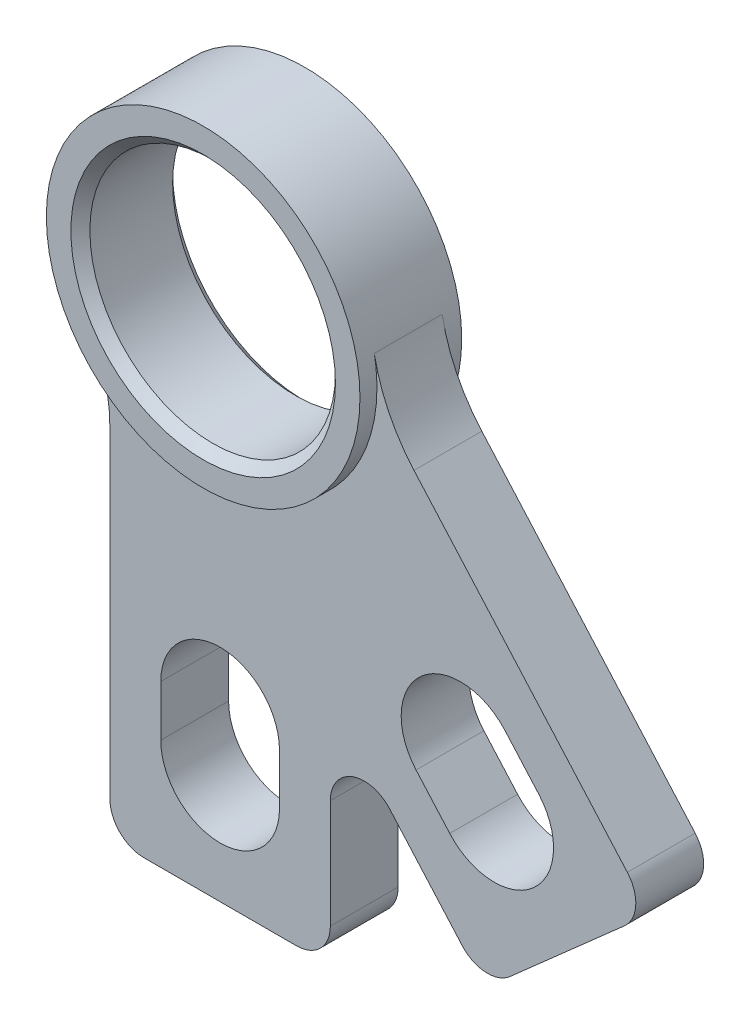
SolidWorks part; units mm, degrees
material "AISI 4130 Steel, annealed at 865C"
ref_plane "X-Y Datum" through (0, 0, 0) normal (0, 0, 1) x (1, 0, 0)
ref_plane "X-Z Datum" through (0, 0, 0) normal (0, 1, 0) x (1, 0, 0)
ref_plane "Y-Z Datum" through (0, 0, 0) normal (1, 0, 0) x (0, 0, -1)
sketch "Sketch1" plane through (0, 0, 0) normal (0, 0, 1) x (1, 0, 0)
  line L0 (0, -38.6896) -> (0, -33.9271) construction
  line L1 (-5.5562, -38.6896) -> (-5.5562, -33.9271)
  line L2 (5.5562, -38.6896) -> (5.5562, -33.9271)
  line L3 (25.6601, -29.0407) -> (22.5066, -25.4718) construction
  line L4 (21.4963, -32.7197) -> (18.3429, -29.1508)
  line L5 (29.8238, -25.3617) -> (26.6703, -21.7927)
  line L6 (-10.3187, -15.7343) -> (-10.3187, -49.0083)
  line L7 (-10.3187, -49.0083) -> (10.3187, -49.0083)
  line L10 (24.7599, -43.6058) -> (40.2252, -29.9408)
  line L11 (40.2252, -29.9408) -> (18.151, -4.9585)
  line L12 (10.3187, -49.0083) -> (10.3187, -27.2621)
  line L14 (0, -44.2458) -> (0, -49.0083) construction
  line L15 (29.3391, -33.2044) -> (32.4926, -36.7733) construction
  line L16 (28.2471, -23.5772) -> (31.816, -20.4237) construction
  line L17 (-5.5562, -36.3083) -> (-10.3187, -36.3083) construction
  line L18 (-10.3187, -23.6083) -> (10.3187, -23.6083) construction
  line L19 (10.3187, -23.6083) -> (10.3187, -49.0083) construction
  line L20 (5.5562, -36.3083) -> (10.3187, -36.3083) construction
  line L21 (0, -28.3708) -> (0, -23.6083) construction
  line L22 (24.7599, -43.6058) -> (7.9415, -24.5716) construction
  line L23 (7.9415, -24.5716) -> (23.4068, -10.9066) construction
  line L24 (19.9196, -30.9353) -> (16.3507, -34.0887) construction
  line L25 (18.8276, -21.308) -> (15.6741, -17.7391) construction
  line L29 (24.7599, -43.6058) -> (10.3187, -27.2621)
  line L33 (214.751, -243.0437) -> (0, 0) construction
  line L34 (0, -321.4016) -> (0, 0) construction
  circle A0 centre (0, 0) radius 11.4954
  arc A1 (-5.5562, -38.6896) -> (5.5562, -38.6896) centre (0, -38.6896) ccw
  arc A2 (5.5562, -33.9271) -> (-5.5562, -33.9271) centre (0, -33.9271) ccw
  arc A3 (21.4963, -32.7197) -> (29.8238, -25.3617) centre (25.6601, -29.0407) ccw
  arc A4 (26.6703, -21.7927) -> (18.3429, -29.1508) centre (22.5066, -25.4718) ccw
  arc A5 (14.4367, 2.6681) -> (-12.5852, -7.5598) centre (0, 0) ccw
  arc A6 (18.151, -4.9585) -> (14.4367, 2.6681) centre (30.0474, 5.5531) cw
  arc A7 (-10.3187, -15.7343) -> (-12.5852, -7.5598) centre (-26.1937, -15.7343) ccw
  arc A14 (-12.5852, -7.5598) -> (14.4367, 2.6681) centre (0, 0) ccw
  point P5 (0, -36.3083)
  point P11 (24.0833, -27.2562)
  point P24 (32.4926, -36.7733)
  point P39 (29.3391, -33.2044)
  dimension "D1" = 22.9908
  dimension "D2" = 14.6812
  dimension "D8" = 15.875
  dimension "D6" = 7.9375
  dimension "D7" = 7.874
  dimension "D3" = 20.6375
  dimension "D4" = 4.7625
  dimension "D5" = 25.4
extrude "Boss-Extrude2" add sketch "Sketch1" along normal mid plane 9.525 contours A5 A14 A0 region at (-5.05, 13.3422, 0)
extrude "Boss-Extrude3" add sketch "Sketch1<4>" along normal mid plane 6.35 contours L29 L10 L11 A6 A14 A7 L6 L7 A4 L5 A3 L4 A2 L2 A1 L1 region at (10.1036, -26.6437, 0)
sketch "Sketch1<4>" plane through (0, 0, 0) normal (0, 0, 1) x (1, 0, 0) same geometry as "Sketch1"
fillet "Fillet1" radius 3.175 5 edges at (-10.3187, -49.0083, 0) (40.2252, -29.9408, 0) (10.3187, -27.2621, 0) (24.7599, -43.6058, 0) (10.3187, -49.0083, 0)
sketch "Sketch4" plane through (0, 0, 4.7625) normal (0, 0, 1) x (1, 0, 0)
  point P0 (0, 0)
sketch "Sketch5" plane through (0, 0, -4.7625) normal (0, 0, -1) x (-1, 0, 0)
  point P0 (0, 0)
  point P1 (-28.1649, 3.919)
ref_point "Point1"
chamfer "Chamfer1" distance 0.889 angle 45 2 edges at (11.4954, 0, 4.7625) (11.4954, 0, -4.7625)
